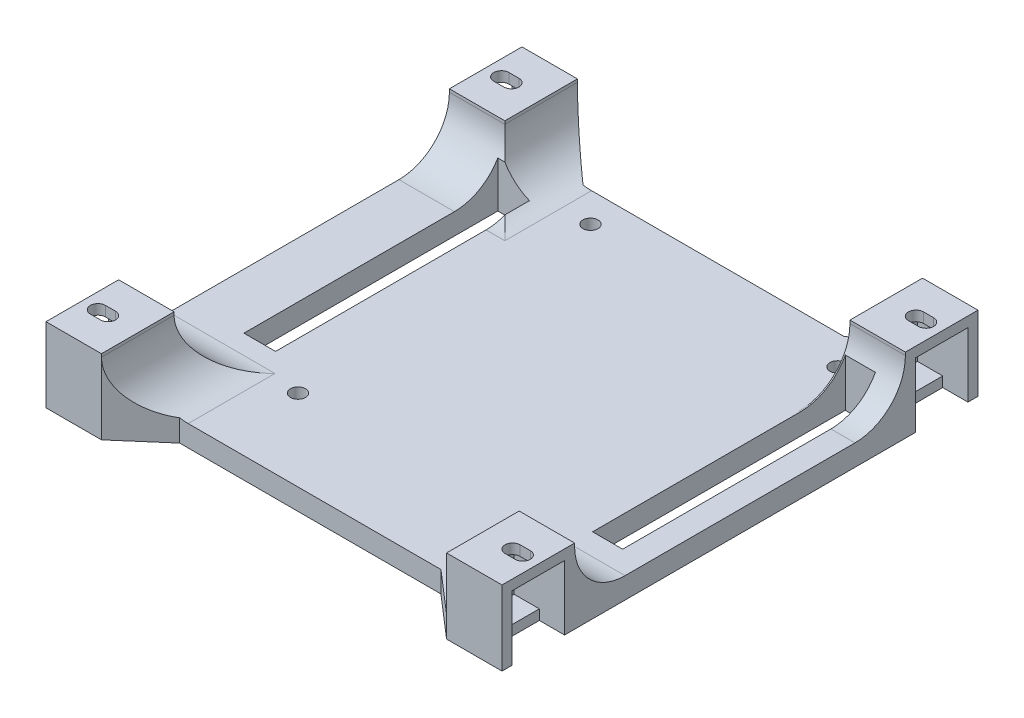
SolidWorks part; units mm, degrees
ref_plane "Front Plane" through (0, 0, 0) normal (0, 0, 1) x (1, 0, 0)
ref_plane "Top Plane" through (0, 0, 0) normal (0, 1, 0) x (1, 0, 0)
ref_plane "Right Plane" through (0, 0, 0) normal (1, 0, 0) x (0, 0, -1)
sketch "Sketch1" plane through (0, 0, 0) normal (1, 0, 0) x (0, 0, -1)
  line L0 (-18.2958, 19.4412) -> (-18.2958, 25.4412) construction
  line L2 (61.7042, 25.4412) -> (61.7042, 19.4412) construction
  line L5 (-18.2958, 22.4412) -> (61.7042, 22.4412) construction
  line L7 (-23.4958, 17.0412) -> (-13.0958, 17.0412)
  line L8 (-23.4958, 17.0412) -> (-23.4958, 27.8412)
  line L9 (-23.4958, 27.8412) -> (-13.0958, 27.8412)
  line L10 (-13.0958, 17.0412) -> (-13.0958, 27.8412)
  line L11 (-23.4958, 17.0412) -> (-13.0958, 27.8412) construction
  line L12 (-23.4958, 27.8412) -> (-13.0958, 17.0412) construction
  line L13 (56.5042, 17.0412) -> (66.9042, 17.0412)
  line L14 (56.5042, 17.0412) -> (56.5042, 27.8412)
  line L15 (56.5042, 27.8412) -> (66.9042, 27.8412)
  line L16 (66.9042, 17.0412) -> (66.9042, 27.8412)
  line L17 (56.5042, 17.0412) -> (66.9042, 27.8412) construction
  line L18 (56.5042, 27.8412) -> (66.9042, 17.0412) construction
  line L32 (-18.2958, 22.4412) -> (-78.2958, 22.4412) construction
  line L33 (-78.2958, 22.4412) -> (-78.2958, -17.0042) construction
  line L36 (-25.4958, 15.0412) -> (-11.0958, 15.0412)
  line L37 (-25.4958, 15.0412) -> (-25.4958, 29.8412)
  line L38 (-25.4958, 29.8412) -> (-11.0958, 29.8412)
  line L39 (-11.0958, 15.0412) -> (-11.0958, 29.8412)
  line L40 (-25.4958, 15.0412) -> (-11.0958, 29.8412) construction
  line L41 (-25.4958, 29.8412) -> (-11.0958, 15.0412) construction
  line L42 (54.5042, 29.8412) -> (68.9042, 29.8412)
  line L43 (54.5042, 29.8412) -> (54.5042, 15.0412)
  line L44 (54.5042, 15.0412) -> (68.9042, 15.0412)
  line L45 (68.9042, 29.8412) -> (68.9042, 15.0412)
  line L46 (54.5042, 29.8412) -> (68.9042, 15.0412) construction
  line L47 (54.5042, 15.0412) -> (68.9042, 29.8412) construction
  dimension "D1" = 10.4
  dimension "D3" = 10.4
  dimension "D4" = 10.8
  dimension "D9" = 2
  dimension "D10" = 2
  dimension "D11" = 2
  dimension "D12" = 2
extrude "Boss-Extrude1" add sketch "Sketch1" along normal blind 5
sketch "Sketch2" plane through (5, 0, 0) normal (1, 0, 0) x (0, 0, -1)
  line L0 (-25.4958, 29.8412) -> (-11.0958, 29.8412)
  line L1 (-11.0958, 29.8412) -> (-11.0958, 15.0412)
  line L2 (-25.4958, 29.8412) -> (-25.4958, 15.0412)
  line L3 (-23.4958, 27.8412) -> (-13.0958, 27.8412)
  line L4 (-13.0958, 27.8412) -> (-13.0958, 15.0412)
  line L5 (-25.4958, 15.0412) -> (-11.0958, 15.0412) construction
  line L6 (-13.0958, 15.0412) -> (-11.0958, 15.0412)
  line L7 (-23.4958, 27.8412) -> (-23.4958, 15.0412)
  line L8 (-23.4958, 15.0412) -> (-25.4958, 15.0412)
  line L9 (54.5042, 29.8412) -> (68.9042, 29.8412)
  line L10 (68.9042, 29.8412) -> (68.9042, 15.0412)
  line L11 (54.5042, 29.8412) -> (54.5042, 15.0412)
  line L12 (56.5042, 27.8412) -> (66.9042, 27.8412)
  line L13 (66.9042, 27.8412) -> (66.9042, 15.0412)
  line L14 (66.9042, 15.0412) -> (68.9042, 15.0412)
  line L15 (56.5042, 27.8412) -> (56.5042, 15.0412)
  line L16 (54.5042, 15.0412) -> (68.9042, 15.0412) construction
  line L17 (56.5042, 15.0412) -> (54.5042, 15.0412)
extrude "Boss-Extrude2" add sketch "Sketch2" along normal blind 5
sketch "Sketch3" plane through (0, 0, 0) normal (-1, 0, 0) x (0, 0, 1)
  line L1 (-68.9042, 29.8412) -> (-54.5042, 29.8412)
  line L2 (-68.9042, 29.8412) -> (-68.9042, 15.0412)
  line L3 (-68.9042, 15.0412) -> (-54.5042, 15.0412)
  line L4 (-54.5042, 29.8412) -> (-54.5042, 15.0412)
  line L5 (11.0958, 29.8412) -> (25.4958, 29.8412)
  line L6 (11.0958, 29.8412) -> (11.0958, 15.0412)
  line L7 (11.0958, 15.0412) -> (25.4958, 15.0412)
  line L8 (25.4958, 29.8412) -> (25.4958, 15.0412)
extrude "Boss-Extrude3" add sketch "Sketch3" along normal blind 1
sketch "Sketch4" plane through (-1, 0, 0) normal (-1, 0, 0) x (0, 0, 1)
  line L0 (-61.7042, 29.8412) -> (-61.7042, 15.0412) construction
  line L1 (-54.5042, 29.8412) -> (-68.9042, 29.8412) construction
  line L2 (-68.9042, 15.0412) -> (-54.5042, 15.0412) construction
  line L3 (18.2958, 29.8412) -> (18.2958, 15.0412) construction
  line L4 (25.4958, 29.8412) -> (11.0958, 29.8412) construction
  line L5 (11.0958, 15.0412) -> (25.4958, 15.0412) construction
  line L6 (-61.7042, 15.0412) -> (18.2958, 15.0412)
  line L7 (18.2958, 15.0412) -> (18.2958, 19.2412)
  line L8 (18.2958, 19.2412) -> (-61.7042, 19.2412)
  line L9 (-61.7042, 19.2412) -> (-61.7042, 15.0412)
extrude "Boss-Extrude4" add sketch "Sketch4" along normal blind 34.22
sketch "Sketch19" plane through (0, 29.8412, 0) normal (0, 1, 0) x (1, 0, 0)
  line L0 (10, 61.7042) -> (-1, 61.7042) construction
  line L1 (10, 68.9042) -> (10, 54.5042) construction
  line L2 (-1, 54.5042) -> (-1, 68.9042) construction
  line L3 (4.9011, 61.7042) -> (6.9011, 61.7042) construction
  line L4 (4.9011, 63.2042) -> (6.9011, 63.2042)
  line L5 (4.9011, 60.2042) -> (6.9011, 60.2042)
  line L6 (4.5, 54.5042) -> (4.5, -11.0958) construction
  line L7 (10, 54.5042) -> (-1, 54.5042) construction
  line L8 (10, -11.0958) -> (-1, -11.0958) construction
  line L9 (4.5, 21.7042) -> (-35.22, 21.7042) construction
  line L10 (-35.22, -18.2958) -> (-35.22, 61.7042) construction
  line L11 (4.9011, -18.2958) -> (6.9011, -18.2958) construction
  line L12 (4.9011, -19.7958) -> (6.9011, -19.7958)
  line L13 (4.9011, -16.7958) -> (6.9011, -16.7958)
  arc A0 (4.9011, 63.2042) -> (4.9011, 60.2042) centre (4.9011, 61.7042) ccw
  arc A1 (6.9011, 60.2042) -> (6.9011, 63.2042) centre (6.9011, 61.7042) ccw
  arc A2 (4.9011, -19.7958) -> (4.9011, -16.7958) centre (4.9011, -18.2958) cw
  arc A3 (6.9011, -16.7958) -> (6.9011, -19.7958) centre (6.9011, -18.2958) cw
  point P8 (5.9011, 61.7042)
  point P25 (5.9011, -18.2958)
  point P30 (0, 0)
  point P31 (0, 0)
  point P32 (4.767, 61.7042)
  point P33 (5.046, 61.7042)
  point P34 (0, 0)
  point P35 (5.4757, 61.7042)
  point P36 (4.163, 61.7042)
  point P37 (6.9011, 61.7042)
  dimension "D1" = 2
extrude "Cut-Extrude9" cut sketch "Sketch19" against normal blind 5
sketch "Sketch20" plane through (0, 19.2412, 0) normal (0, 1, 0) x (1, 0, 0)
  line L0 (-1, -11.0958) -> (10, -11.0958)
  line L1 (10, -11.0958) -> (10, 54.5042)
  line L2 (10, 54.5042) -> (-1, 54.5042)
  line L3 (-1, 54.5042) -> (-1, -11.0958)
extrude "Boss-Extrude8" add sketch "Sketch20" against normal up to surface (4.2 mm away) up to face at (1.178, 15.0412, -21.7042)
mirror "Mirror1" about plane through (-35.22, 0, 0) normal (-1, 0, 0) of bodies 141 139
sketch "Sketch9" plane through (0, 19.2412, 0) normal (0, 1, 0) x (1, 0, 0)
  line L0 (-1, 68.9042) -> (-1, 61.7042)
  line L1 (-1, 54.5042) -> (-1, 68.9042) construction
  line L2 (-1, 61.7042) -> (-9.311, 61.7042)
  line L3 (-69.44, 61.7042) -> (-1, 61.7042) construction
  line L4 (-9.311, 61.7042) -> (-1, 68.9042)
  line L5 (-35.22, 61.7042) -> (-35.22, 81.0456) construction
  line L6 (-61.129, 61.7042) -> (-69.44, 68.9042)
  line L7 (-69.44, 61.7042) -> (-61.129, 61.7042)
  line L8 (-69.44, 68.9042) -> (-69.44, 61.7042)
  line L9 (10, 21.7042) -> (-50.0448, 21.7042) construction
  line L11 (-69.44, -25.4958) -> (-69.44, -18.2958)
  line L12 (-69.44, -18.2958) -> (-61.129, -18.2958)
  line L13 (-61.129, -18.2958) -> (-69.44, -25.4958)
  line L14 (-9.311, -18.2958) -> (-1, -25.4958)
  line L15 (-1, -18.2958) -> (-9.311, -18.2958)
  line L16 (-1, -25.4958) -> (-1, -18.2958)
  line L17 (10, -11.0958) -> (10, 54.5042) construction
extrude "Boss-Extrude7" add sketch "Sketch9" against normal up to surface (4.2 mm away) up to face at (-35.22, 15.0412, -21.7042)
sketch "Sketch12" plane through (0, 19.2412, 0) normal (0, 1, 0) x (1, 0, 0)
  circle A0 centre (-4.7838, -2.1732) radius 1.5
  circle A1 centre (-53.7838, -2.1732) radius 1.5
  circle A2 centre (-53.7838, 55.8268) radius 1.5
  circle A3 centre (-4.7838, 55.8268) radius 1.5
extrude "Cut-Extrude2" cut sketch "Sketch12" against normal blind 10
sketch "Sketch13" plane through (0, 19.2412, 0) normal (0, 1, 0) x (1, 0, 0)
  line L1 (-0.7503, 3.2111) -> (5.219, 3.2111)
  line L2 (-0.7503, 3.2111) -> (-0.7503, 53.3377)
  line L3 (-0.7503, 53.3377) -> (5.219, 53.3377)
  line L4 (5.219, 3.2111) -> (5.219, 53.3377)
extrude "Cut-Extrude3" cut sketch "Sketch13" against normal blind 10
sketch "Sketch14" plane through (0, 19.2412, 0) normal (0, 1, 0) x (1, 0, 0)
  line L1 (-63.1677, 2.759) -> (-69.44, 2.759)
  line L2 (-63.1677, 2.759) -> (-63.1677, 53.1122)
  line L3 (-63.1677, 53.1122) -> (-69.44, 53.1122)
  line L4 (-69.44, 2.759) -> (-69.44, 53.1122)
extrude "Cut-Extrude4" cut sketch "Sketch14" against normal blind 10
fillet "Fillet2" radius 10 8 edges at (4.5, 19.2412, 11.0958) (4.5, 19.2412, -54.5042) (-74.94, 19.2412, 11.0958) (-74.94, 19.2412, -54.5042) (-65.2845, 19.2412, -65.3042) (-65.2845, 19.2412, 21.8958) (2.2344, 19.2412, -53.3377) (-66.3039, 19.2412, -53.1122)
